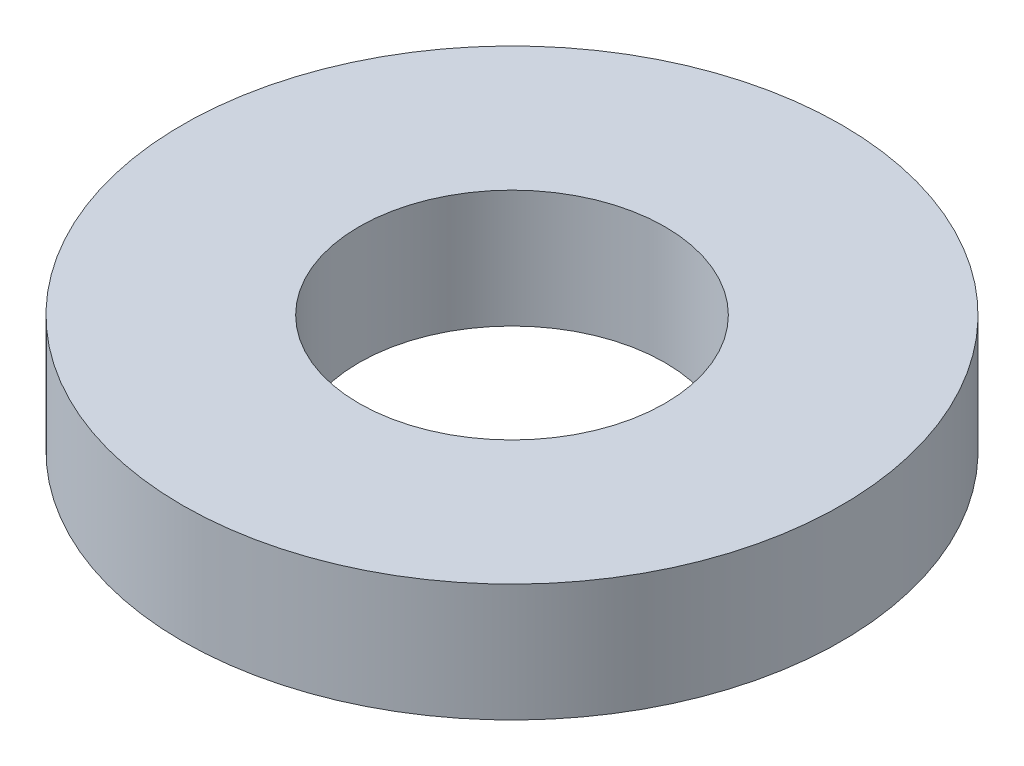
SolidWorks part; units mm, degrees
ref_plane "Front Plane" through (0, 0, 0) normal (0, 0, 1) x (1, 0, 0)
ref_plane "Top Plane" through (0, 0, 0) normal (0, 1, 0) x (1, 0, 0)
ref_plane "Right Plane" through (0, 0, 0) normal (1, 0, 0) x (0, 0, -1)
sketch "Sketch1" plane through (0, 0, 0) normal (0, 1, 0) x (1, 0, 0)
  circle A0 centre (0, 0) radius 70
  dimension "FLANGE_OD" = 140
extrude "Boss-Extrude1" add sketch "Sketch1" along normal blind 25
sketch "Sketch2" plane through (0, 0, 0) normal (0, 1, 0) x (1, 0, 0)
  circle A0 centre (0, 0) radius 32.5
  dimension "BORE_D" = 65
extrude "Cut-Extrude1" cut sketch "Sketch2" along normal through all
sketch "Sketch3" plane through (0, 25, 0) normal (0, 1, 0) x (1, 0, 0)
  circle A0 centre (0, 0) radius 26.2117 construction
  circle A1 centre (-26.2117, 0) radius 4.5123
  dimension "BOLT_D" = 9.0247
  dimension "BOLT_PCD" = 52.4233
extrude "Cut-Extrude2" cut sketch "Sketch3" against normal blind 21.5954 rebuild error yes
pattern_circular "CirPattern1" count 6 over 360 rebuild error yes
